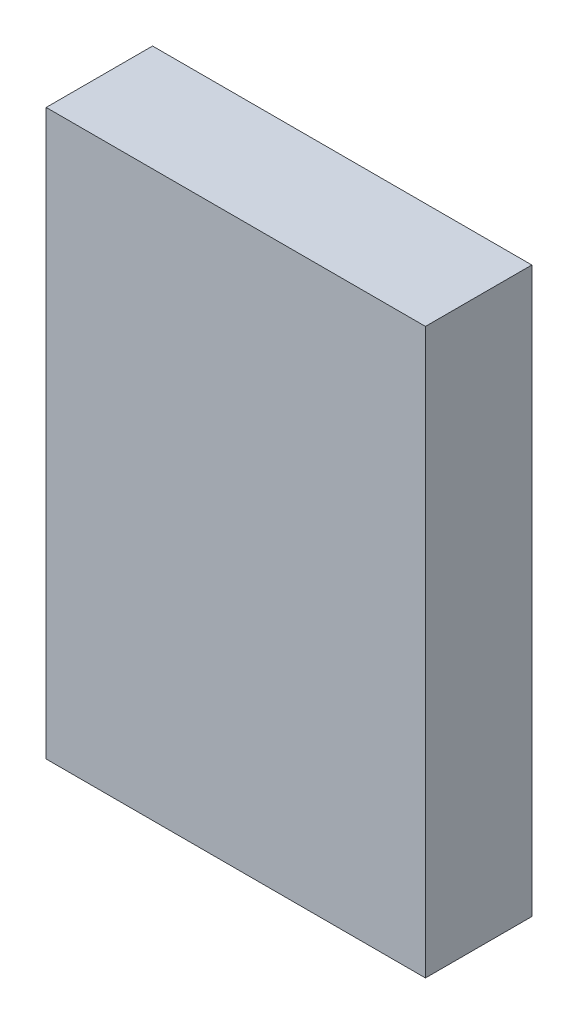
SolidWorks part; units mm, degrees
ref_plane "Front Plane" through (0, 0, 0) normal (0, 0, 1) x (1, 0, 0)
ref_plane "Top Plane" through (0, 0, 0) normal (0, 1, 0) x (1, 0, 0)
ref_plane "Right Plane" through (0, 0, 0) normal (1, 0, 0) x (0, 0, -1)
sketch "Sketch1" plane through (0, 0, 0) normal (0, 0, 1) x (1, 0, 0)
  line L1 (-41, 61) -> (41, 61)
  line L2 (-41, 61) -> (-41, -61)
  line L3 (-41, -61) -> (41, -61)
  line L4 (41, 61) -> (41, -61)
  point P4 (0, -61)
  point P7 (-41, 0)
  dimension "D1" = 82
  dimension "D2" = 122
extrude "Boss-Extrude1" add sketch "Sketch1" against normal blind 23
sketch "Sketch2" plane through (0, 0, -23) normal (0, 0, -1) x (-1, 0, 0)
  line L0 (-41, 61) -> (41, 61) construction
  line L1 (-38, 58) -> (38, 58)
  line L2 (-38, 58) -> (-38, -58)
  line L3 (-38, -58) -> (38, -58)
  line L4 (38, 58) -> (38, -58)
  line L5 (41, -61) -> (-41, -61) construction
  line L6 (-41, -61) -> (-41, 61) construction
  line L7 (41, 61) -> (41, -61) construction
  point P6 (0, -58)
  dimension "D1" = 3
  dimension "D2" = 3
  dimension "D3" = 3
  dimension "D4" = 3
extrude "Cut-Extrude1" cut sketch "Sketch2" against normal offset from surface (21 mm away) 2 up to face at (0, 0, 0)
sketch "Sketch6" plane through (0, 0, -23) normal (0, 0, -1) x (-1, 0, 0)
  line L0 (-38, 58) -> (-38, -58) construction
  line L1 (-39, 59) -> (39, 59)
  line L2 (-39, 59) -> (-39, -59)
  line L3 (-39, -59) -> (39, -59)
  line L4 (39, 59) -> (39, -59)
  line L5 (38, 58) -> (-38, 58) construction
  line L6 (38, -58) -> (38, 58) construction
  line L8 (-38, -58) -> (38, -58) construction
  dimension "D1" = 1
  dimension "D2" = 1
  dimension "D3" = 1
  dimension "D4" = 1
extrude "Cut-Extrude3" cut sketch "Sketch6" against normal blind 2
sketch "Sketch3" plane through (0, 0, -2) normal (0, 0, -1) x (-1, 0, 0)
  line L1 (38, 58) -> (-38, 58) construction
  line L2 (-38, 58) -> (-38, -58) construction
  circle A0 centre (30, 50) radius 4
  circle A1 centre (-30, 50) radius 4
  circle A2 centre (30, -20) radius 4
  circle A3 centre (-30, -20) radius 4
  dimension "D1" = 8
  dimension "D3" = 2
  dimension "D4" = 8
  dimension "D2" = 8
  dimension "D5" = 2
extrude "Boss-Extrude2" add sketch "Sketch3" along normal blind 3
sketch "Sketch4" plane through (0, 0, -5) normal (0, 0, -1) x (-1, 0, 0)
  circle A0 centre (-30, 50) radius 2
  circle A1 centre (30, 50.0168) radius 2
  circle A2 centre (30.0196, -19.9832) radius 2
  circle A3 centre (-29.9804, -20) radius 2
  dimension "D1" = 4
  dimension "D2" = 2
  dimension "D3" = 2
extrude "Boss-Extrude3" add sketch "Sketch4" along normal blind 17
sketch "Sketch5" plane through (0, 0, -22) normal (0, 0, -1) x (-1, 0, 0)
  circle A0 centre (-30, 50) radius 0.75
  circle A1 centre (30, 50.0168) radius 0.75
  circle A2 centre (30.0196, -19.9832) radius 0.75
  circle A3 centre (-29.9804, -20) radius 0.75
  dimension "D1" = 1.5
  dimension "D2" = 2
  dimension "D3" = 2
extrude "Cut-Extrude2" cut sketch "Sketch5" against normal blind 4.7
